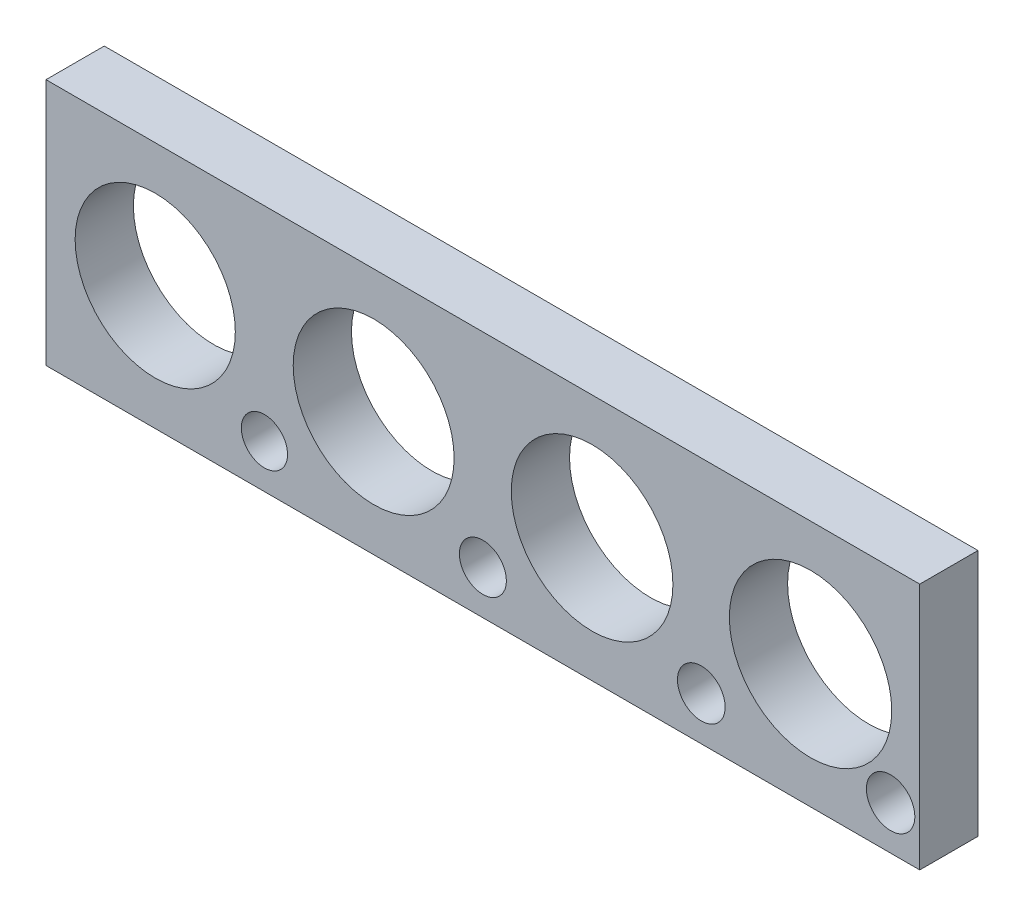
SolidWorks part; units mm, degrees
ref_plane "Front Plane" through (0, 0, 0) normal (0, 0, 1) x (1, 0, 0)
ref_plane "Top Plane" through (0, 0, 0) normal (0, 1, 0) x (1, 0, 0)
ref_plane "Right Plane" through (0, 0, 0) normal (1, 0, 0) x (0, 0, -1)
sketch "Coupon_plate_profile" plane through (0, 0, 0) normal (0, 0, 1) x (1, 0, 0)
  line L1 (-60, -17) -> (60, -17)
  line L2 (-60, -17) -> (-60, 17)
  line L3 (-60, 17) -> (60, 17)
  line L4 (60, -17) -> (60, 17)
  dimension "D1" = 120
  dimension "D2" = 34
  dimension "D3" = 60
  dimension "D4" = 17
extrude "Coupon_plate" add sketch "Coupon_plate_profile" along normal blind 8
sketch "Bearing_seat_trial_22p0_22p1_22p2_22p3" plane through (0, 0, 0) normal (0, 0, 1) x (1, 0, 0)
  circle A0 centre (-45, 0) radius 11
  circle A1 centre (-15, 0) radius 11.05
  circle A2 centre (15, 0) radius 11.1
  circle A3 centre (45, 0) radius 11.15
  dimension "D1" = 22
  dimension "D2" = 22.1
  dimension "D3" = 22.2
  dimension "D4" = 22.3
  dimension "D5" = 15
  dimension "D6" = 45
  dimension "D7" = 15
  dimension "D8" = 45
extrude "Bearing_fit_trial_through" cut sketch "Bearing_seat_trial_22p0_22p1_22p2_22p3" along normal through all from offset 1 offset against normal yes
sketch "Dowel_trial_6p35_6p45_6p55_6p65" plane through (0, 0, 0) normal (0, 0, 1) x (1, 0, 0)
  circle A0 centre (-30, -11) radius 3.175
  circle A1 centre (0, -11) radius 3.225
  circle A2 centre (30, -11) radius 3.275
  circle A3 centre (56, -11) radius 3.325
  dimension "D1" = 6.35
  dimension "D2" = 6.45
  dimension "D3" = 6.55
  dimension "D4" = 6.65
  dimension "D5" = 30
  dimension "D6" = 56
  dimension "D7" = 30
  dimension "D8" = 11
extrude "Dowel_fit_trial_through" cut sketch "Dowel_trial_6p35_6p45_6p55_6p65" along normal through all from offset 1 offset against normal yes
